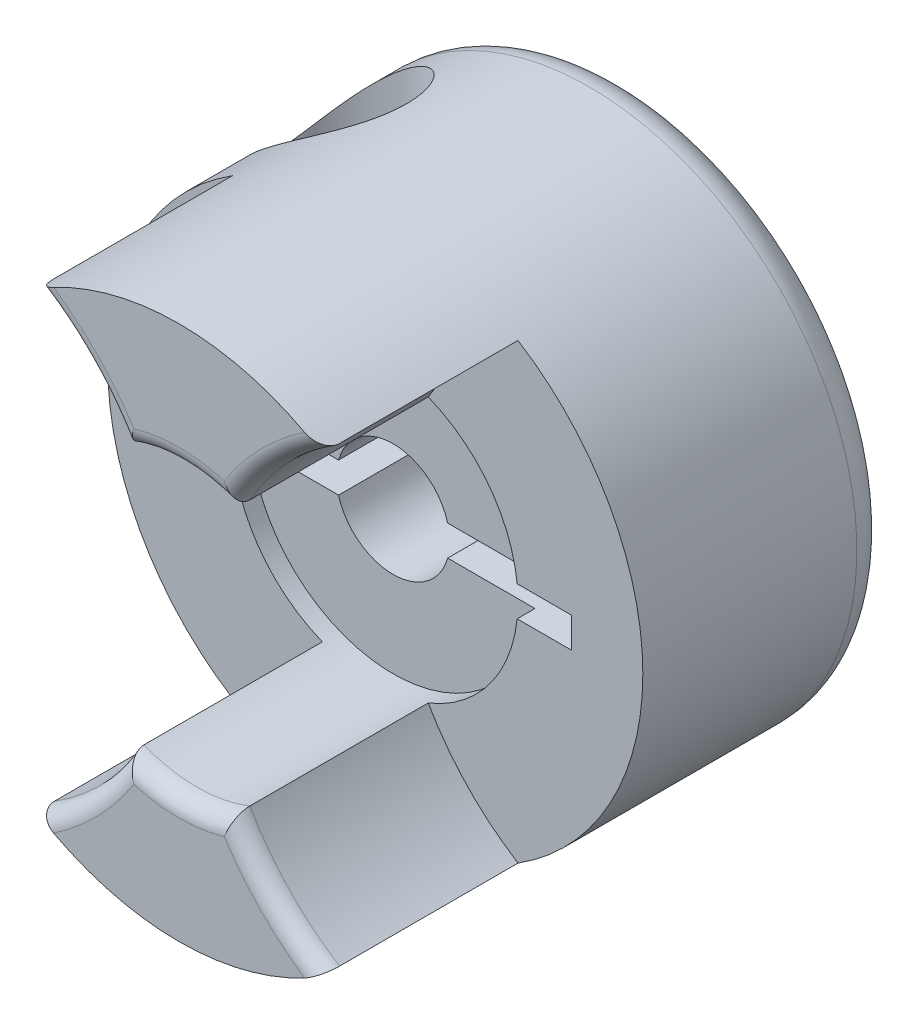
SolidWorks part; units mm, degrees
ref_plane "Front Plane" through (0, 0, 0) normal (0, 0, 1) x (1, 0, 0)
ref_plane "Top Plane" through (0, 0, 0) normal (0, 1, 0) x (1, 0, 0)
ref_plane "Right Plane" through (0, 0, 0) normal (1, 0, 0) x (0, 0, -1)
sketch "Sketch1" plane through (0, 0, 0) normal (0, 0, 1) x (1, 0, 0)
  circle A0 centre (0, 0) radius 15
extrude "Boss-Extrude1" add sketch "Sketch1" along normal blind 25
sketch "Sketch3" plane through (0, 0, 25) normal (0, 0, 1) x (1, 0, 0)
  arc A0 (2.9688, -7.4288) -> (2.9688, 7.4288) centre (16, 0) ccw
  arc A1 (-2.9688, 7.4288) -> (-2.9688, -7.4288) centre (-16, 0) ccw
  arc A2 (2.9688, 7.4288) -> (-2.9688, 7.4288) centre (0, 0) ccw
  arc A3 (-2.9688, -7.4288) -> (2.9688, -7.4288) centre (0, 0) ccw
extrude "Cut-Extrude1" cut sketch "Sketch3" against normal blind 11
sketch "Sketch4" plane through (0, 0, 14) normal (0, 0, 1) x (1, 0, 0)
  circle A0 centre (0, 0) radius 3.175
  dimension "D1" = 6.35
extrude "Cut-Extrude2" cut sketch "Sketch4" against normal blind 14
sketch "Sketch5" plane through (0, 0, 14) normal (0, 0, 1) x (1, 0, 0)
  circle A0 centre (0, 0) radius 8
extrude "Cut-Extrude3" cut sketch "Sketch5" against normal blind 1
sketch "Sketch6" plane through (0, 0, 14) normal (0, 0, 1) x (1, 0, 0)
  line L1 (-17.8419, 0.85) -> (11, 0.85)
  line L2 (-17.8419, 0.85) -> (-17.8419, -0.85)
  line L3 (-17.8419, -0.85) -> (11, -0.85)
  line L4 (11, 0.85) -> (11, -0.85)
extrude "Cut-Extrude4" cut sketch "Sketch6" against normal blind 14
sketch "Sketch7" plane through (0, 0, 0) normal (0, 0, -1) x (-1, 0, 0)
  line L1 (-11, 0.85) -> (-3.0591, 0.85)
  line L2 (-11, 0.85) -> (-11, -0.85)
  line L3 (-11, -0.85) -> (-3.0591, -0.85)
  line L4 (-3.0591, 0.85) -> (-3.0591, -0.85)
extrude "Boss-Extrude2" add sketch "Sketch7" against normal blind 2
chamfer "Chamfer1" distance 11 angle 45 1 edges at (11, 0, 2)
sketch "Sketch8" plane through (0, 0, 0) normal (0, 1, 0) x (1, 0, 0)
  circle A0 centre (-9, -7) radius 2
extrude "Cut-Extrude5" cut sketch "Sketch8" against normal blind 14 and the other way blind 14
ref_plane "Plane1" through (0, 15, 0) normal (0, 1, 0) x (1, 0, 0)
sketch "Sketch9" plane through (0, 15, 0) normal (0, 1, 0) x (1, 0, 0)
  circle A0 centre (-9, -7) radius 3.75
extrude "Cut-Extrude6" cut sketch "Sketch9" against normal blind 11
fillet "Fillet1" radius 2 1 edges at (15, 0, 0)
fillet "Fillet2" radius 1 6 edges at (0, -8, 25) (0, 8, 25) (5.1605, 10.3685, 25) (-5.1605, 10.3685, 25) (-5.1605, -10.3685, 25) (5.1605, -10.3685, 25)
